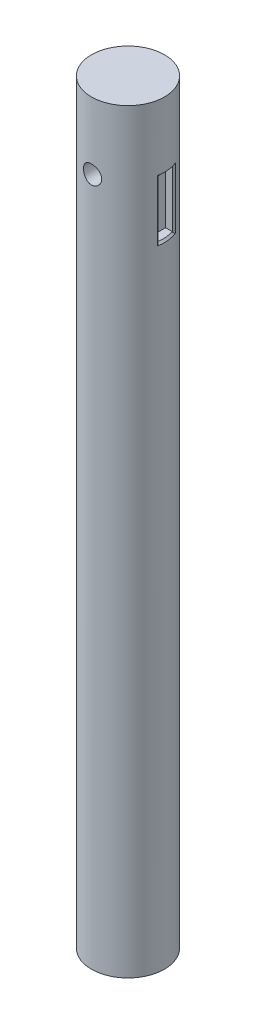
SolidWorks part; units mm, degrees
material "AISI 1020"
ref_plane "Alzado" through (0, 0, 0) normal (0, 0, 1) x (1, 0, 0)
ref_plane "Planta" through (0, 0, 0) normal (0, 1, 0) x (1, 0, 0)
ref_plane "Vista lateral" through (0, 0, 0) normal (1, 0, 0) x (0, 0, -1)
sketch "Croquis1" plane through (0, 0, 0) normal (0, 1, 0) x (1, 0, 0)
  circle A0 centre (0, 0) radius 19.05
  dimension "D1" = 38.1
extrude "Saliente-Extruir1" add sketch "Croquis1" along normal blind 394
sketch "Croquis2" plane through (0, 0, 0) normal (0, 0, 1) x (1, 0, 0)
  line L0 (19.05, 394) -> (-19.05, 394) construction
  circle A0 centre (0, 359) radius 4.765
  dimension "D1" = 9.53
  dimension "D2" = 35
extrude "Cortar-Extruir1" cut sketch "Croquis2" against normal through all both and the other way through all
ref_plane "Plano1" through (19.05, 0, 0) normal (1, 0, 0) x (0, 0, -1)
sketch "Croquis4" plane through (19.05, 0, 0) normal (1, 0, 0) x (0, 0, -1)
  line L1 (-2.2829, 329.2) -> (6.0071, 329.2)
  line L2 (-2.2829, 329.2) -> (-2.2829, 359)
  line L3 (-2.2829, 359) -> (6.0071, 359)
  line L4 (6.0071, 329.2) -> (6.0071, 359)
  line L5 (-2.2829, 329.2) -> (6.0071, 359) construction
  line L6 (-2.2829, 359) -> (6.0071, 329.2) construction
  line L7 (19.05, 394) -> (-19.05, 394) construction
  point P0 (1.8621, 344.1)
  dimension "D1" = 29.8
  dimension "D2" = 8.29
  dimension "D3" = 35
extrude "Cortar-Extruir2" cut sketch "Croquis4" against normal blind 5.45 and the other way through all
chamfer "Chaflán1" distance 1 angle 45 4 edges at (18.0781, 344.1, -6.0071) (18.9542, 359, -1.9083) (18.9542, 329.2, -1.9083) (18.9127, 344.1, 2.2829) first distance on face at (0, 0, 19.05)
